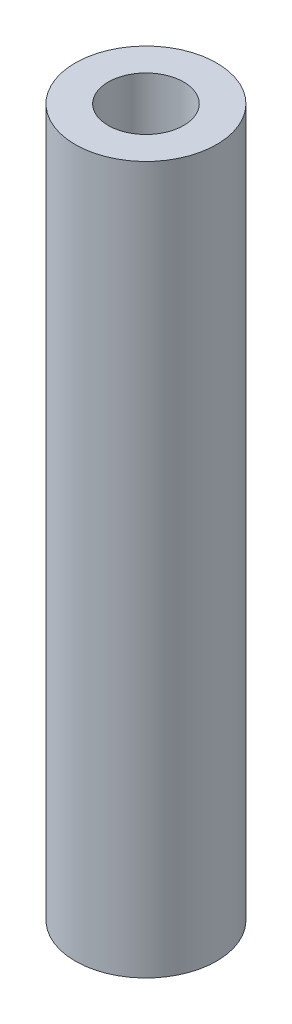
SolidWorks part; units mm, degrees
material "AISI 1045 Steel, cold drawn"
ref_plane "Front Plane" through (0, 0, 0) normal (0, 0, 1) x (1, 0, 0)
ref_plane "Top Plane" through (0, 0, 0) normal (0, 1, 0) x (1, 0, 0)
ref_plane "Right Plane" through (0, 0, 0) normal (1, 0, 0) x (0, 0, -1)
sketch "Sketch1" plane through (0, 0, 0) normal (0, 1, 0) x (1, 0, 0)
  circle A0 centre (0, 0) radius 3
  dimension "D1" = 6
extrude "Boss-Extrude1" add sketch "Sketch1" along normal blind 30
hole_wizard "M3 Clearance Hole1" positions "Sketch2" profile "Sketch3" hole size "M3" standard "ANSI Metric" end condition through all
sketch "Sketch2" plane through (0, 30, 0) normal (0, 1, 0) x (1, 0, 0)
  point P0 (0, 0)
sketch "Sketch3" plane through (0, 30, 0) normal (1, 0, 0) x (0, 0, 1)
  line L0 (0, 0) -> (0, 30)
  line L1 (0, 30) -> (1.6, 30)
  line L2 (1.6, 30) -> (1.6, 0)
  line L5 (1.6, 0) -> (0, 0)
  line L11 (0, -6.35) -> (0, 107.95) construction
  dimension "Thru Hole Dia." = 3.2
  dimension "Thru Hole Depth" = 30
